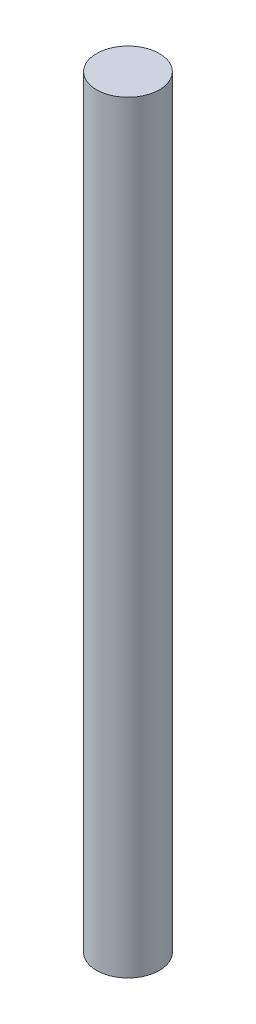
SolidWorks part; units mm, degrees
ref_plane "Front Plane" through (0, 0, 0) normal (0, 0, 1) x (1, 0, 0)
ref_plane "Top Plane" through (0, 0, 0) normal (0, 1, 0) x (1, 0, 0)
ref_plane "Right Plane" through (0, 0, 0) normal (1, 0, 0) x (0, 0, -1)
sketch "Elevation Bar" plane through (0, 0, 0) normal (0, 1, 0) x (1, 0, 0)
  circle A0 centre (0, 0) radius 30.226
  dimension "D1" = 60.452
extrude "Elevation Bar Part" add sketch "Elevation Bar" along normal blind 734.06
sketch "Sketch2" plane through (0, 0, 0) normal (0, 0, 1) x (1, 0, 0)
  line L0 (0, 0) -> (172.1794, 0) construction
  line L1 (-30.226, 0) -> (-30.226, 734.06) construction
  line L2 (-30.226, 734.06) -> (30.226, 734.06) construction
  line L3 (30.226, 734.06) -> (30.226, 0) construction
  line L4 (30.226, 0) -> (30.226, 734.06) construction
  line L5 (636.651, 40.7185) -> (27.051, 40.7185) construction
  line L6 (636.651, 53.4185) -> (27.051, 53.4185)
  line L7 (636.651, 53.4185) -> (636.651, 28.0185)
  line L8 (636.651, 28.0185) -> (27.051, 28.0185)
  line L9 (27.051, 53.4185) -> (27.051, 28.0185)
  line L10 (-30.226, 93.98) -> (30.226, 93.98) construction
  line L11 (33.2486, 0) -> (-33.2486, 0) construction
  line L12 (30.226, 185.42) -> (-30.226, 185.42) construction
  line L13 (30.226, 276.86) -> (-30.226, 276.86) construction
  line L14 (30.226, 368.3) -> (-30.226, 368.3) construction
  line L15 (30.226, 459.74) -> (-30.226, 459.74) construction
  line L16 (30.226, 551.18) -> (-30.226, 551.18) construction
  line L17 (30.226, 642.62) -> (-30.226, 642.62) construction
  line L18 (30.226, 73.152) -> (750.8896, 73.152) construction
  circle A0 centre (576.5632, 40.7185) radius 41.275 construction
  circle A1 centre (87.1388, 40.7185) radius 41.275 construction
  circle A2 centre (331.851, 40.7185) radius 41.275 construction
  point P24 (331.851, 40.7185)
  dimension "D2" = 82.55
  dimension "D1" = 609.6
  dimension "D3" = 25.4
  dimension "D4" = 244.7122
  dimension "D5" = 244.7122
  dimension "D6" = 93.98
  dimension "D7" = 185.42
  dimension "D8" = 276.86
  dimension "D9" = 368.3
  dimension "D10" = 459.74
  dimension "D11" = 551.18
  dimension "D12" = 642.62
  dimension "D13" = 73.152
sketch "Sketch4" plane through (0, 0, 0) normal (0, 0, 1) x (1, 0, 0)
  line L0 (-30.226, 182.88) -> (-30.226, 101.727) construction
  line L1 (52.451, 101.727) -> (27.051, 101.727) construction
  line L2 (-30.226, 0) -> (-30.226, 734.06) construction
  line L3 (30.226, 734.06) -> (30.226, 0) construction
  line L4 (-30.226, 182.88) -> (30.226, 101.727) construction
  line L5 (30.226, 101.727) -> (-30.226, 101.727) construction
  line L6 (27.051, 101.727) -> (-30.226, 182.88) construction
  line L7 (27.051, 101.727) -> (27.051, 40.7185) construction
  line L8 (30.226, 226.8605) -> (203.668, 53.4185) construction
  line L10 (30.226, 73.152) -> (750.8896, 73.152) construction
  line L11 (636.651, 53.4185) -> (27.051, 53.4185) construction
  circle A0 centre (52.451, 101.727) radius 20.6375
  circle A1 centre (52.451, 101.727) radius 25.4
  circle A2 centre (52.451, 101.727) radius 22.225 construction
  circle A3 centre (-55.626, 182.88) radius 25.4
  circle A4 centre (81.026, 104.2185) radius 50.8 construction
  dimension "D1" = 50.8
  dimension "D2" = 41.275
  dimension "D3" = 1.5875
  dimension "D4" = 3.175
  dimension "D5" = 182.88
  dimension "D8" = 101.6
  dimension "D6" = 50.8
  dimension "D7" = 81.153
  dimension "D9" = 45
  dimension "D10" = 54.786
  dimension "D11" = 53.317
  dimension "D12" = 48.3085
ref_plane "Plane1" through (0, 53.4185, 0) normal (0, 1, 0) x (1, 0, 0)
equation "\"D5@Sketch2\"=\"D4@Sketch2\""
